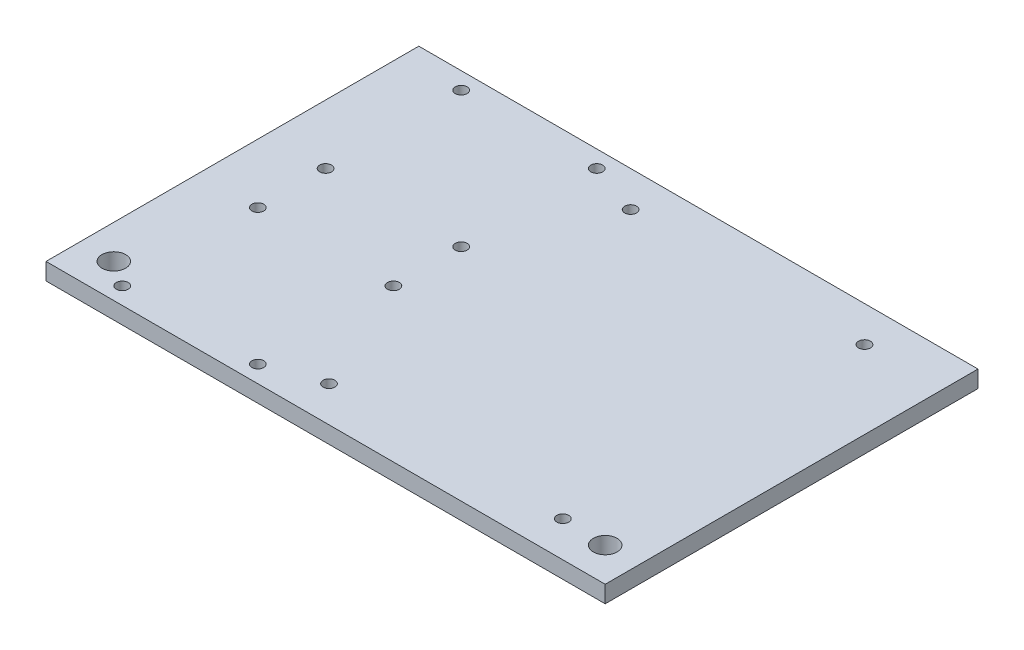
SolidWorks part; units mm, degrees
ref_plane "Front Plane" through (0, 0, 0) normal (0, 0, 1) x (1, 0, 0)
ref_plane "Top Plane" through (0, 0, 0) normal (0, 1, 0) x (1, 0, 0)
ref_plane "Right Plane" through (0, 0, 0) normal (1, 0, 0) x (0, 0, -1)
sketch "Sketch1" plane through (0, 0, 0) normal (0, 1, 0) x (1, 0, 0)
  line L1 (-82.5, 55) -> (82.5, 55)
  line L2 (-82.5, 55) -> (-82.5, -55)
  line L3 (-82.5, -55) -> (82.5, -55)
  line L4 (82.5, 55) -> (82.5, -55)
  line L5 (-82.5, 55) -> (82.5, -55) construction
  line L6 (-82.5, -55) -> (82.5, 55) construction
  line L7 (59.5, -44.5) -> (-9.5, -44.5) construction
  line L8 (59.5, -44.5) -> (59.5, 44.5) construction
  line L9 (59.5, 44.5) -> (-9.5, 44.5) construction
  line L10 (-9.5, -44.5) -> (-9.5, 44.5) construction
  line L11 (59.5, -44.5) -> (-9.5, 44.5) construction
  line L12 (59.5, 44.5) -> (-9.5, -44.5) construction
  line L13 (-25, -50) -> (-65, -50) construction
  line L14 (-25, -50) -> (-25, -10) construction
  line L15 (-25, -10) -> (-65, -10) construction
  line L16 (-65, -50) -> (-65, -10) construction
  line L17 (-25, -50) -> (-65, -10) construction
  line L18 (-25, -10) -> (-65, -50) construction
  line L19 (-25, 10) -> (-65, 10) construction
  line L20 (-25, 10) -> (-25, 50) construction
  line L21 (-25, 50) -> (-65, 50) construction
  line L22 (-65, 10) -> (-65, 50) construction
  line L23 (-25, 10) -> (-65, 50) construction
  line L24 (-25, 50) -> (-65, 10) construction
  circle A0 centre (72.5, -45) radius 3.5
  circle A1 centre (-72.5, -45) radius 3.5
  circle A2 centre (59.5, -44.5) radius 1.75
  circle A3 centre (-9.5, -44.5) radius 1.75
  circle A4 centre (-25, -50) radius 1.75
  circle A5 centre (-65, -50) radius 1.75
  circle A6 centre (-65, -10) radius 1.75
  circle A7 centre (-25, -10) radius 1.75
  circle A8 centre (-65, 10) radius 1.75
  circle A9 centre (-25, 10) radius 1.75
  circle A10 centre (-65, 50) radius 1.75
  circle A11 centre (-25, 50) radius 1.75
  circle A12 centre (-9.5, 44.5) radius 1.75
  circle A13 centre (59.5, 44.5) radius 1.75
  point P0 (0, 0)
  point P10 (25, 0)
  point P15 (-45, 30)
  point P16 (-45, -30)
  dimension "D3" = 7
  dimension "D15" = 3.5
  dimension "D1" = 110
  dimension "D2" = 165
  dimension "D4" = 10
  dimension "D5" = 10
  dimension "D6" = 10
  dimension "D7" = 89
  dimension "D8" = 69
  dimension "D9" = 25
  dimension "D10" = 40
  dimension "D11" = 40
  dimension "D12" = 20
  dimension "D13" = 10
  dimension "D14" = 45
extrude "Boss-Extrude1" add sketch "Sketch1" along normal blind 5
